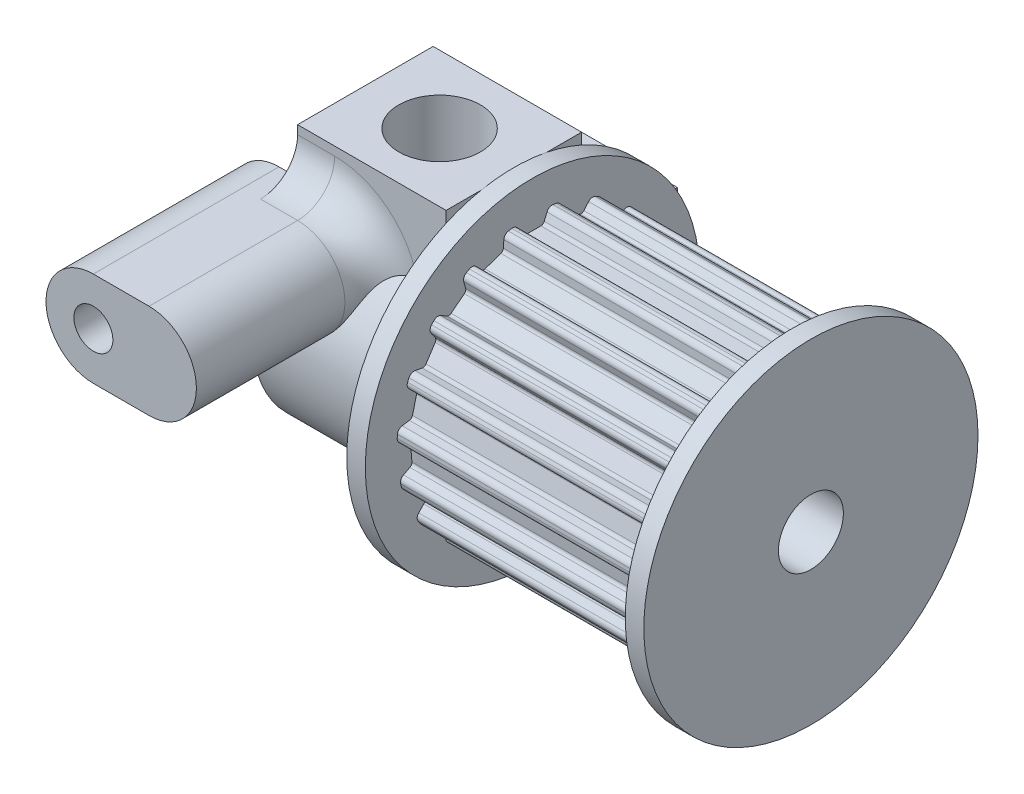
SolidWorks part; units mm, degrees
material "PLA Black"
ref_plane "Front" through (0, 0, 0) normal (0, 0, 1) x (1, 0, 0)
ref_plane "Top" through (0, 0, 0) normal (0, 1, 0) x (1, 0, 0)
ref_plane "Right" through (0, 0, 0) normal (1, 0, 0) x (0, 0, -1)
sketch "Sketch1" plane through (0, 0, 0) normal (1, 0, 0) x (0, 0, -1)
  line L0 (1.118, 1) -> (-1.118, 1) construction
  line L1 (-3.65, 4.8249) -> (3.65, 4.8249)
  line L2 (4.8249, 3.65) -> (4.8249, -3.65)
  line L3 (0, 0) -> (11.6334, 0) construction
  line L4 (0, 0) -> (0, 8.6732) construction
  arc A0 (-1.118, 1) -> (1.118, 1) centre (0, 0) ccw construction
  circle A1 centre (0, 0) radius 1.75
  arc A2 (4.8249, -3.65) -> (-3.65, 4.8249) centre (0, 0) cw
  arc A3 (4.8249, 3.65) -> (3.65, 4.8249) centre (0, 0) ccw
  dimension "D1" = 3
  dimension "D3" = 0.25
  dimension "D5" = 6.05
  dimension "D2" = 1
  dimension "D4" = 7.3
extrude "Boss-Extrude1" add sketch "Sketch1" along normal mid plane 8
sketch "Sketch2" plane through (0, 4.8249, 0) normal (0, 1, 0) x (1, 0, 0)
  circle A0 centre (0, 0) radius 2.2
  dimension "D1" = 4.4
extrude "Cut-Extrude1" cut sketch "Sketch2" against normal blind 5
sketch "Sketch7" plane through (4, 0, 0) normal (1, 0, 0) x (0, 0, -1)
  circle A0 centre (0, 0) radius 1.75 construction
  circle A1 centre (0, 0) radius 7.3
  circle A2 centre (0, 0) radius 1.75
  dimension "D1" = 14.6
extrude "Boss-Extrude5" add sketch "Sketch7" along normal blind 15
sketch "Sketch8" plane through (19, 0, 0) normal (1, 0, 0) x (0, 0, -1)
  line L0 (-0.4541, 6.5499) -> (0.4528, 6.5499)
  line L1 (0.6374, 6.6734) -> (0.7865, 7.0333)
  line L2 (-0.6389, 6.6734) -> (-0.788, 7.0333)
  line L6 (0, 9.2013) -> (0, 0) construction
  arc A0 (0.4528, 6.5499) -> (0.6374, 6.6734) centre (0.4526, 6.7499) ccw
  arc A1 (-0.4541, 6.5499) -> (-0.6389, 6.6734) centre (-0.4541, 6.7499) cw
  arc A2 (0.7865, 7.0333) -> (1.1093, 7.2152) centre (1.0638, 6.9187) cw
  arc A3 (-0.788, 7.0333) -> (-1.1108, 7.215) centre (-1.0652, 6.9185) ccw
  circle A4 centre (0, 0) radius 7.3 construction
  arc A5 (-1.1108, 7.215) -> (1.1093, 7.2152) centre (0, 0) cw
  point P3 (-0.0007, 6.5499)
  point P15 (0, 9.84)
extrude "Cut-Extrude3" cut sketch "Sketch8" against normal up to surface (15 mm away) up to face at (4, 0, -7.3)
pattern_circular "CirPattern1" count 19 over 360 about axis through (19, 0, 0) along (-1, 0, 0) of "Cut-Extrude3"
sketch "Sketch9" plane through (19, 0, 0) normal (1, 0, 0) x (0, 0, -1)
  circle A0 centre (0, 0) radius 9
  circle A1 centre (0, 0) radius 1.75 construction
  circle A2 centre (0, 0) radius 1.75
  dimension "D1" = 18
extrude "Boss-Extrude6" add sketch "Sketch9" along normal blind 1
sketch "Sketch10" plane through (4, 0, 0) normal (-1, 0, 0) x (0, 0, 1)
  circle A0 centre (0, 0) radius 9
  circle A1 centre (0, 0) radius 9 construction
  circle A2 centre (0, 0) radius 1.75 construction
  circle A3 centre (0, 0) radius 1.75
extrude "Boss-Extrude7" add sketch "Sketch10" against normal blind 1
sketch "Sketch3" plane through (0, 0, -4.8249) normal (0, 0, -1) x (-1, 0, 0)
  circle A0 centre (0, 0) radius 2.2
  dimension "D1" = 4.4
extrude "Cut-Extrude2" cut sketch "Sketch3" against normal blind 5
sketch "Sketch4" plane through (0, 4.8249, 0) normal (0, 1, 0) x (1, 0, 0)
  line L0 (4, 3.65) -> (-4, 3.65) construction
  line L2 (4, -3.65) -> (-4, -3.65) construction
  line L3 (-4, 3.65) -> (-4, -3.65) construction
  line L4 (4, 3.65) -> (-4, 3.65)
  line L5 (4, 3.65) -> (4, -3.65)
  line L6 (4, -3.65) -> (-4, -3.65)
  line L7 (-4, 3.65) -> (-4, -3.65)
  line L8 (4, 7.3) -> (4, -7.3) construction
  circle A0 centre (0, 0) radius 2.2 construction
  circle A1 centre (0, 0) radius 2.2
extrude "Boss-Extrude2" add sketch "Sketch4" along normal blind 4
sketch "Sketch5" plane through (0, 0, -4.8249) normal (0, 0, -1) x (-1, 0, 0)
  line L0 (-4, 3.65) -> (4, 3.65) construction
  line L1 (4, -3.65) -> (4, 3.65) construction
  line L2 (-4, -3.65) -> (4, -3.65) construction
  line L4 (-4, 3.65) -> (4, 3.65)
  line L5 (4, -3.65) -> (4, 3.65)
  line L6 (-4, -3.65) -> (4, -3.65)
  line L7 (-4, -3.65) -> (-4, 3.65)
  line L8 (-4, -7.3) -> (-4, 7.3) construction
  circle A0 centre (0, 0) radius 2.2 construction
  circle A1 centre (0, 0) radius 2.2
extrude "Boss-Extrude3" add sketch "Sketch5" along normal blind 4
ref_axis "Axis1" through (4, 0, 0) along (-1, 0, 0)
sketch "Sketch6" plane through (0, 0, 3.65) normal (0, 0, 1) x (1, 0, 0)
  line L0 (-4, 8.8249) -> (-4, 4.8249) construction
  line L2 (-2, 6.3555) -> (-5, 6.3555)
  line L3 (-5, 1.2545) -> (-2, 1.2545)
  line L6 (4, 0) -> (-4, 0) construction
  circle A0 centre (-5, 3.805) radius 1.0505
  arc A1 (-5, 6.3555) -> (-5, 1.2545) centre (-5, 3.805) ccw
  arc A2 (-2, 6.3555) -> (-2, 1.2545) centre (-2, 3.805) cw
  dimension "D1" = 2.101
  dimension "D2" = 3.805
  dimension "D3" = 1.5
  dimension "D4" = 1
  dimension "D5" = 3
extrude "Boss-Extrude4" add sketch "Sketch6" along normal blind 10
fillet "Fillet1" radius 2 2 edges at (-0.6029, 5.9388, 3.65) (-3, 6.3555, 3.65)
equation "\"knee_angle\"= 70"
equation "\"ankle_angle\" = 80"
equation "\"hip_angle\" = 40"
equation "\"spring_ankle_parallel_arm_diameter\"= 1.1"
equation "\"spring_ankle_parallel_arm_length\"= 13"
equation "\"spring_ankle_parallel_intern_diameter\"= 5.7"
equation "\"spring_ankle_parallel_angle\"= \"ankle_angle\""
equation "\"spring_ankle_parallel_turns\"= 3"
equation "\"spring_ankle_parallel_pitch\"= \"spring_ankle_parallel_arm_diameter\" * 1.01"
equation "\"spring_ankle_parallel_cutting_distance\"= (1-\"spring_ankle_parallel_angle\" / 360) * \"spring_ankle_parallel_pitch\""
equation "\"spring_ankle_serial_arm_diameter\"= 1.91"
equation "\"spring_ankle_serial_arm_length\"= 10"
equation "\"spring_ankle_serial_intern_diameter\"= 5.7"
equation "\"spring_ankle_serial_angle\"= \"90\""
equation "\"spring_ankle_serial_turns\"= 3"
equation "\"spring_ankle_serial_pitch\"= \"spring_ankle_serial_arm_diameter\" * 1.01"
equation "\"spring_ankle_serial_cutting_distance\"= (1-\"spring_ankle_serial_angle\" / 360) * \"spring_ankle_serial_pitch\""
equation "\"spring_knee_parallel_arm_diameter\"= 1.1"
equation "\"spring_knee_parallel_arm_length\"= 13"
equation "\"spring_knee_parallel_intern_diameter\"= 5.7"
equation "\"spring_knee_parallel_angle\"= -\"knee_angle\" + 90"
equation "\"spring_knee_parallel_turns\"= 3"
equation "\"spring_knee_parallel_pitch\"= \"spring_knee_parallel_arm_diameter\" * 1.01"
equation "\"spring_knee_parallel_cutting_distance\"= (1-(\"spring_knee_parallel_angle\") / 360) * \"spring_knee_parallel_pitch\""
equation "\"spring_knee_serial_arm_diameter\"= 1.91"
equation "\"spring_knee_serial_arm_length\"= 10"
equation "\"spring_knee_serial_intern_diameter\"= 5.7"
equation "\"spring_knee_serial_angle\"= \"90\""
equation "\"spring_knee_serial_turns\"= 3"
equation "\"spring_knee_serial_pitch\"= \"spring_knee_serial_arm_diameter\" * 1.01"
equation "\"spring_knee_serial_cutting_distance\"= (1-\"spring_knee_serial_angle\" / 360) * \"spring_knee_serial_pitch\""
equation "\"D2@Sketch6\" = ( \"spring_knee_serial_intern_diameter\" + \"spring_knee_serial_arm_diameter\" ) / 2"
equation "\"D1@Sketch6\"=\"spring_knee_serial_arm_diameter\"*1.1"
